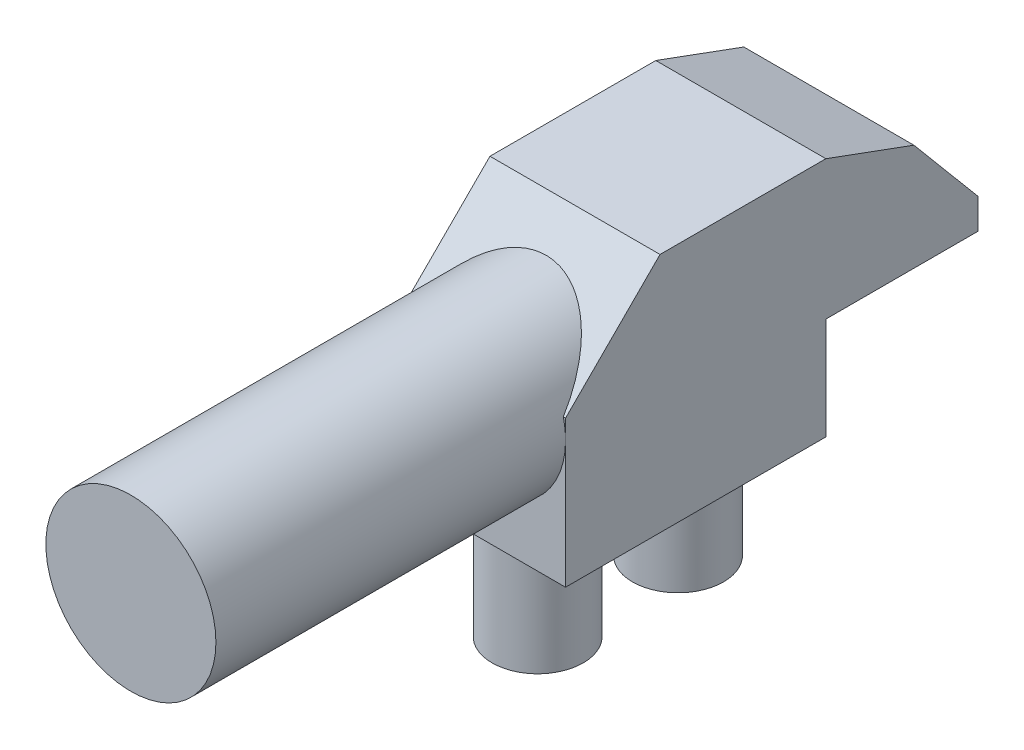
SolidWorks part; units mm, degrees
ref_plane "Front Plane" through (0, 0, 0) normal (0, 0, 1) x (1, 0, 0)
ref_plane "Top Plane" through (0, 0, 0) normal (0, 1, 0) x (1, 0, 0)
ref_plane "Right Plane" through (0, 0, 0) normal (1, 0, 0) x (0, 0, -1)
sketch "Sketch1" plane through (0, 0, 0) normal (0, 1, 0) x (1, 0, 0)
  line L1 (-1.8, 2.755) -> (1.8, 2.755)
  line L2 (-1.8, 2.755) -> (-1.8, -2.755)
  line L3 (-1.8, -2.755) -> (1.8, -2.755)
  line L4 (1.8, 2.755) -> (1.8, -2.755)
  line L5 (-1.8, 2.755) -> (1.8, -2.755) construction
  line L6 (-1.8, -2.755) -> (1.8, 2.755) construction
  point P0 (0, 0)
  dimension "D1" = 5.51
  dimension "D2" = 3.6
extrude "Boss-Extrude1" add sketch "Sketch1" along normal blind 2.41 and the other way blind 2.69
sketch "Sketch2" plane through (0, 0, 2.755) normal (0, 0, 1) x (1, 0, 0)
  circle A0 centre (0, 0) radius 1.8
  dimension "D1" = 3.6
extrude "Boss-Extrude2" add sketch "Sketch2" along normal blind 7.4
ref_plane "Plane1" through (0, -0.53, 0) normal (0, -1, 0) x (-1, 0, 0)
sketch "Sketch3" plane through (0, -2.69, 0) normal (0, -1, 0) x (1, 0, 0)
  line L0 (1.8, 10.155) -> (-1.8, 10.155) construction
  circle A0 centre (0, 1.545) radius 0.965
  circle A1 centre (0, -1.425) radius 0.965
  dimension "D1" = 2.97
  dimension "D2" = 1.93
  dimension "D3" = 8.61
extrude "Boss-Extrude3" add sketch "Sketch3" along normal blind 2.41
sketch "Sketch4" plane through (0, 0, 0) normal (1, 0, 0) x (0, 0, -1)
  line L0 (2.755, -0.53) -> (5.975, -0.53)
  line L1 (-1.98, -0.53) -> (1.98, -0.53) construction
  line L2 (2.755, -2.69) -> (2.755, 2.41) construction
  line L3 (5.975, -0.53) -> (5.975, 0.1109)
  line L4 (5.975, 0.1109) -> (4.6184, 1.7263)
  line L5 (4.6184, 1.7263) -> (2.755, 2.41)
  line L6 (2.755, 2.41) -> (2.755, -0.53)
  line L8 (-10.155, 1.8) -> (-10.155, -1.8) construction
  dimension "D1" = 16.13
extrude "Boss-Extrude4" add sketch "Sketch4" along normal up to surface and the other way up to surface up to face at (1.8, -0.112, 0.551) other way up to face at (-1.8, -0.112, 0.551)
chamfer "Chamfer1" distance 2 angle 45 1 edges at (0, 2.41, 2.755)
